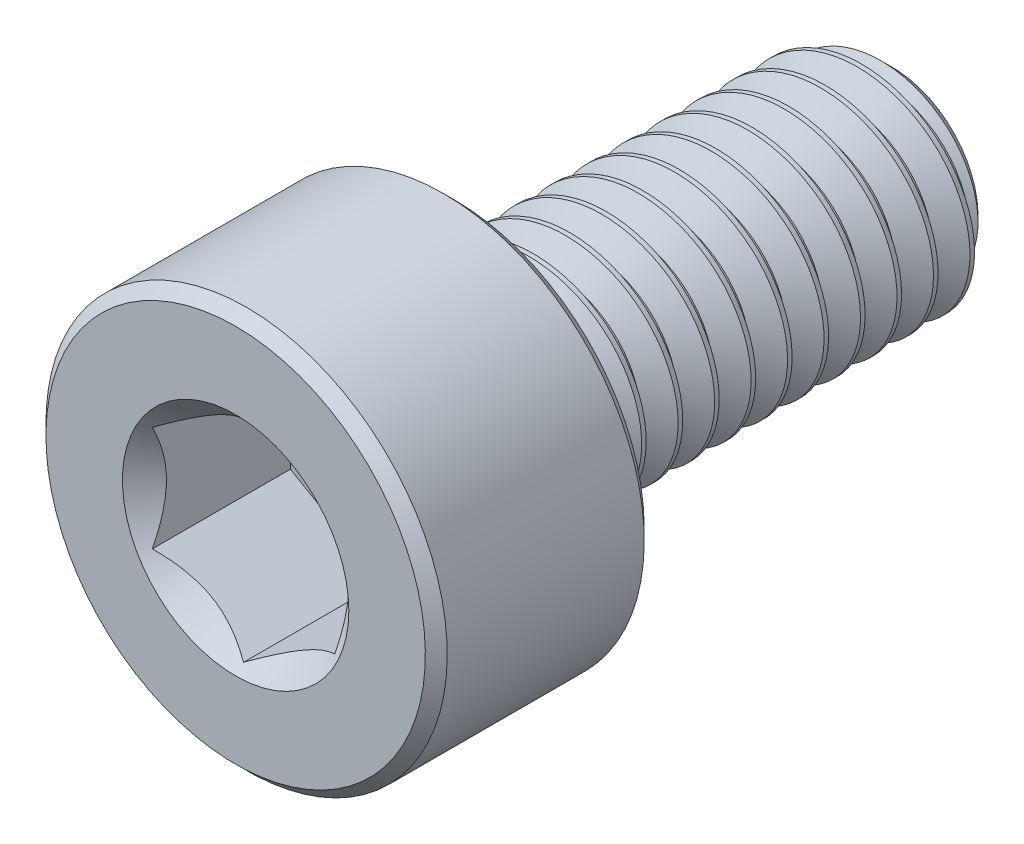
SolidWorks part; units mm, degrees
ref_plane "Front Plane" through (0, 0, 0) normal (0, 0, 1) x (1, 0, 0)
ref_plane "Top Plane" through (0, 0, 0) normal (0, 1, 0) x (1, 0, 0)
ref_plane "Right Plane" through (0, 0, 0) normal (1, 0, 0) x (0, 0, -1)
sketch "Sketch1" plane through (0, 0, 0) normal (1, 0, 0) x (0, 0, -1)
  line L0 (-4.5, 0) -> (4.5, 0) construction
  line L1 (4.5, 0) -> (4.5, 1.1752) construction
  line L2 (4.5, 1.1752) -> (4.1752, 1.5) construction
  line L3 (4.1752, 1.5) -> (4.125, 1.5) construction
  line L4 (4.125, 1.5) -> (-1.5, 1.5) construction
  line L5 (-1.5, 1.5) -> (-1.5, 2.75) construction
  line L6 (-1.5, 2.75) -> (-4.5, 2.75) construction
  line L7 (-4.5, 2.75) -> (-4.5, 0) construction
  line L8 (4.5, 1.1752) -> (4.5, 1.5) construction
  line L9 (4.4687, 1.5541) -> (4.7187, 1.1211) construction
  line L10 (4.7187, 1.1211) -> (4.9687, 1.5541) construction
  line L11 (4.9687, 1.5541) -> (4.4687, 1.5541) construction
  line L12 (4.7187, 1.5541) -> (4.7187, 1.5) construction
  line L13 (4.7187, 1.1211) -> (4.7187, 1.1752) construction
  line L14 (4.6875, 1.1752) -> (4.75, 1.1752) construction
  line L15 (4.5, 1.5) -> (4.9375, 1.5) construction
  line L16 (4.4844, 1.5271) -> (4.9531, 1.5271) construction
  line L17 (4.5, 0) -> (4.5, -1.5) construction
  line L18 (-1.65, 2.75) -> (-1.5, 2.6) construction
  line L19 (-4.35, 2.75) -> (-4.5, 2.6) construction
  line L20 (-1.5, 1.5) -> (-1.5, 0) construction
  line L21 (-1.5, 0.75) -> (0.5, 0.75) construction
  line L22 (0.5, 0.75) -> (2.5, 0.75) construction
  line L23 (2.5, 0.75) -> (4.5, 0.75) construction
  line L24 (0.5, 0.75) -> (0.5, 1.5) construction
  line L25 (0.5, 1.5) -> (0.5, 2.75) construction
  line L26 (2.5, 0.75) -> (2.5, 2.75) construction
  point P0 (-4.5, 1.25)
  point P3 (3.25, 1.5)
  point P4 (0, 0)
  point P18 (2.5, 1.5)
  point P22 (4.7187, 1.1752)
  point P24 (4.125, 1.5)
  point P25 (4.7187, 1.5)
  point P28 (4.7187, 1.5271)
  point P29 (3.25, -1.5)
  point P30 (0.5, 1.5)
  point P31 (-3, 2.75)
  point P37 (-2.025, 2.75)
  point P38 (-4.275, 2.75)
  point P45 (0.5, 0.75)
  point P46 (2.5, 0.75)
  dimension "D2" = 0.0625
  dimension "D7" = 0.15
  dimension "D8" = 0.15
  dimension "D9" = 0.15
  dimension "D10" = 0.075
  dimension "D11" = 0.375
  dimension "Drive Size" = 2.5
  dimension "Head Diameter" = 5.5
  dimension "Head Height" = 3
  dimension "Thread Pitch" = 0.5
  dimension "Thread Size" = 3
  dimension "Length" = 6
  dimension "D12" = 0.375
  dimension "D4" = 1.25
  dimension "D3" = 45
sketch "Sketch2" plane through (0, 0, 0) normal (1, 0, 0) x (0, 0, -1)
  line L0 (-4.5, 0) -> (-4.5, 2.6)
  line L1 (-4.35, 2.75) -> (-1.65, 2.75)
  line L2 (-1.5, 2.6) -> (-1.5, 1.65)
  line L4 (4.1752, 1.5) -> (4.5, 1.1752)
  line L5 (4.5, 1.1752) -> (4.5, 0)
  line L6 (-1.5, 2.75) -> (-4.5, 2.75) construction
  line L7 (4.5, 0) -> (-4.5, 0)
  line L8 (-4.35, 2.75) -> (-4.5, 2.6) construction
  line L10 (-4.35, 2.75) -> (-4.5, 2.6)
  line L14 (-1.65, 2.75) -> (-1.5, 2.6) construction
  line L16 (-1.65, 2.75) -> (-1.5, 2.6)
  line L17 (-1.5, 1.5) -> (-1.5, 2.75) construction
  line L19 (-1.35, 1.5) -> (4.1752, 1.5)
  line L20 (4.125, 1.5) -> (-1.5, 1.5) construction
  arc A1 (-1.5, 1.65) -> (-1.35, 1.5) centre (-1.35, 1.65) ccw
revolve "Revolve1" add sketch "Sketch2" angle 360 about L7
sketch "Sketch3" plane through (0, 0, 4.5) normal (0, 0, 1) x (1, 0, 0)
  line L1 (1.25, -0.7217) -> (1.25, 0.7217)
  line L2 (1.25, 0.7217) -> (0, 1.4434)
  line L3 (0, 1.4434) -> (-1.25, 0.7217)
  line L4 (-1.25, 0.7217) -> (-1.25, -0.7217)
  line L5 (-1.25, -0.7217) -> (0, -1.4434)
  line L6 (0, -1.4434) -> (1.25, -0.7217)
  circle A0 centre (0, 0) radius 1.25 construction
  circle A1 centre (0, 0) radius 2.75 construction
  circle A2 centre (0, 0) radius 2.75 construction
  circle A3 centre (0, 0) radius 1.4434 construction
  point P13 (0, 0)
  dimension "D1" = 2.8868
extrude "Cut-Extrude1" cut sketch "Sketch3" against normal offset from surface (2 mm away) 1 up to face at (0, 2.6, 1.5)
sketch "Sketch4" plane through (0, 0, 4.5) normal (0, 0, 1) x (1, 0, 0)
  circle A0 centre (0, 0) radius 1.5516
  dimension "D1" = 3.1033
extrude "Cut-Extrude2" cut sketch "Sketch4" against normal up to vertex (1.5 mm away) draft 45 up to point (0, 2.75, 3)
sketch "Sketch11" plane through (0, 0, 0) normal (1, 0, 0) x (0, 0, -1)
  line L0 (-4.5, 0) -> (4.5, 0) construction
  line L1 (-4.5, 0) -> (4.5, 0) construction
  line L2 (-0.375, 0) -> (-0.375, 1.5) construction
  line L3 (4.125, 1.5) -> (-1.5, 1.5) construction
  line L4 (3.375, 0) -> (3.375, 1.5) construction
  line L6 (4.5, 1.1752) -> (4.5, 1.5) construction
  point P2 (-0.375, 0)
  point P3 (3.375, 0)
  dimension "D1" = 1.125
  dimension "D2" = 1.125
sketch "Sketch6" plane through (0, 0, -4.5) normal (0, 0, -1) x (-1, 0, 0)
  circle A0 centre (0, 0) radius 1.5
curve "Helix/Spiral1" pitch 0.5 height 6.5 radius 1.5 centre (0, 0, -4.5) axis (0, 0, 1) start towards (0, 1, 0)
sketch "Sketch10" plane through (0, 0, 0) normal (1, 0, 0) x (0, 0, -1)
  line L0 (-1.35, -2.75) -> (-1.35, 2.75)
  line L5 (-4.5, 0) -> (4.5, 0) construction
  line L6 (-1.35, 1.5) -> (-1.35, -1.5) construction
  point P3 (-1.35, 0)
split "Split1" trim tools "Sketch10" bodies to split 106 resulting bodies 114 115
sketch "Sketch7" plane through (0, 0, 0) normal (1, 0, 0) x (0, 0, -1)
  line L0 (4.4844, 1.5271) -> (4.9531, 1.5271)
  line L1 (4.9531, 1.5271) -> (4.75, 1.1752)
  line L2 (4.75, 1.1752) -> (4.6875, 1.1752)
  line L3 (4.6875, 1.1752) -> (4.4844, 1.5271)
sweep "Cut-Sweep1" cut profiles "Sketch7" path "Helix/Spiral1" align with end faces yes
sketch "Sketch8" plane through (0, 0, 0) normal (1, 0, 0) x (0, 0, -1)
  line L0 (-1.5, 0) -> (-1.5, 1.5)
  line L1 (-1.35, -1.5) -> (-1.35, 1.5) construction
  line L2 (-1.5, 1.5) -> (-1.35, 1.5)
  line L4 (-1.35, 1.5) -> (-0.484, 0)
  line L5 (-0.484, 0) -> (-1.5, 0)
  line L6 (4.125, 1.5) -> (-1.5, 1.5) construction
  line L7 (-4.5, 0) -> (4.5, 0) construction
  dimension "D1" = 60
revolve "Revolve2" add sketch "Sketch8" angle 360 about L5
equation "\"D2@Sketch1\" = \"Thread Pitch@Sketch1\" / 8"
equation "\"D4@Helix/Spiral1\" = \"Thread Pitch@Sketch1\""
equation "\"D7@Sketch1\" = \"Head Height@Sketch1\" * .05"
equation "\"D8@Sketch1\"=\"D7@Sketch1\""
equation "\"D9@Sketch1\"=\"D7@Sketch1\""
equation "\"D10@Sketch1\"=\"D7@Sketch1\"/2"
equation "\"D11@Sketch1\"=\"D10@Sketch1\"*5"
equation "\"D4@Sketch1\"=\"Thread Pitch@Sketch1\"*2.5"
equation "\"D12@Sketch1\"=\"Thread Pitch@Sketch1\"*.75"
equation "\"D3@Helix/Spiral1\"=\"Length@Sketch1\"+\"Thread Pitch@Sketch1\""
equation "\"D3@Sketch2\"=\"Thread Size@Sketch1\"*0.05"
equation "\"D1@Sketch11\"=\"Length@Sketch1\"*0.1875"
equation "\"D2@Sketch11\"=\"D1@Sketch11\""
equation "\"D1@Sketch4\"=\"D1@Sketch3\"*1.075"
